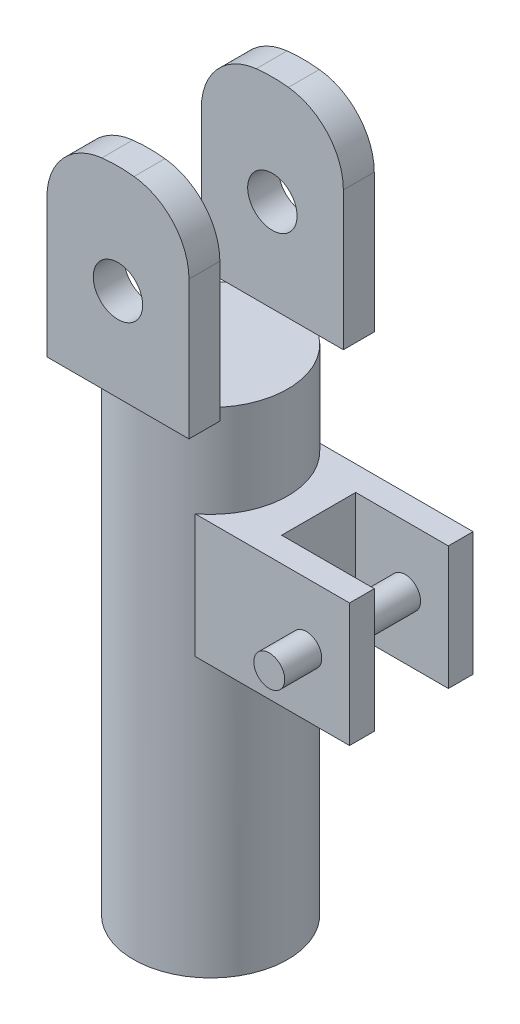
SolidWorks part; units mm, degrees
ref_plane "Front Plane" through (0, 0, 0) normal (0, 0, 1) x (1, 0, 0)
ref_plane "Top Plane" through (0, 0, 0) normal (0, 1, 0) x (1, 0, 0)
ref_plane "Right Plane" through (0, 0, 0) normal (1, 0, 0) x (0, 0, -1)
sketch "Sketch1" plane through (0, 0, 0) normal (0, 1, 0) x (1, 0, 0)
  circle A0 centre (0, 0) radius 12.5
  dimension "D1" = 25
extrude "Boss-Extrude1" add sketch "Sketch1" along normal blind 35
sketch "Sketch3" plane through (0, 0, 0) normal (0, 0, 1) x (1, 0, 0)
  line L5 (12.5, 35) -> (-12.5, 35) construction
  line L6 (12.5, 0) -> (12.5, 35) construction
  line L7 (0, 50) -> (0, 72.8405) construction
  line L8 (-11.5, 35) -> (11.5, 35)
  line L9 (11.5, 35) -> (11.5, 57.4167)
  line L10 (-11.5, 35) -> (-11.5, 57.4167)
  circle A2 centre (0, 50) radius 4
  arc A3 (-2.6077, 67.3551) -> (2.6077, 67.3551) centre (0, 43.9583) cw
  arc A4 (2.6077, 67.3551) -> (11.5, 57.4167) centre (1.5, 57.4167) cw
  arc A5 (-2.6077, 67.3551) -> (-11.5, 57.4167) centre (-1.5, 57.4167) ccw
  point P5 (11.5, 64.5)
  point P10 (-11.5, 64.5)
  dimension "D1" = 15
  dimension "D3" = 23
  dimension "D2" = 10
  dimension "D4" = 1
extrude "Boss-Extrude2" add sketch "Sketch3" along normal mid plane 30
sketch "Sketch4" plane through (0, 0, 0) normal (0, -1, 0) x (1, 0, 0)
  circle A0 centre (0, 0) radius 10
  dimension "D1" = 20
extrude "Cut-Extrude1" cut sketch "Sketch4" against normal blind 30
sketch "Sketch5" plane through (11.5, 0, 0) normal (1, 0, 0) x (0, 0, -1)
  line L0 (15, 67.5) -> (-15, 67.5) construction
  line L1 (-10, 67.5) -> (10, 67.5)
  line L2 (-10, 67.5) -> (-10, 35)
  line L3 (-10, 35) -> (10, 35)
  line L4 (10, 67.5) -> (10, 35)
  line L5 (-15, 35) -> (-4.899, 35) construction
  point P8 (0, 67.5)
  dimension "D1" = 20
extrude "Cut-Extrude2" cut sketch "Sketch5" against normal through all
sketch "Sketch6" plane through (0, 0, 0) normal (0, -1, 0) x (1, 0, 0)
  circle A0 centre (0, 0) radius 10 construction
  circle A1 centre (0, 0) radius 12.5
  circle A2 centre (0, 0) radius 12.5
  circle A3 centre (0, 0) radius 10
  dimension "D1" = 0
extrude "Boss-Extrude3" add sketch "Sketch6" along normal blind 45
sketch "Sketch9" plane through (0, 0, 0) normal (0, 0, 1) x (1, 0, 0)
  line L0 (12.5, -45) -> (12.5, 35) construction
  line L1 (13.5, 0) -> (32.5, 0)
  line L2 (13.5, 0) -> (13.5, 20)
  line L3 (13.5, 20) -> (32.5, 20)
  line L4 (32.5, 0) -> (32.5, 20)
  line L6 (-12.5, -45) -> (12.5, -45) construction
  dimension "D1" = 19
  dimension "D2" = 20
  dimension "D3" = 1
  dimension "D4" = 45
extrude "Boss-Extrude6" add sketch "Sketch9" along normal mid plane 20 separate body
sketch "Sketch10" plane through (13.5, 0, 0) normal (-1, 0, 0) x (0, 0, 1)
  line L4 (-10, 20) -> (-10, 0)
  line L5 (-10, 0) -> (10, 0)
  line L6 (10, 0) -> (10, 20)
  line L7 (10, 20) -> (-10, 20)
  line L8 (-10, 20) -> (-10, 0)
  line L9 (-10, 0) -> (10, 0)
  line L10 (10, 0) -> (10, 20)
  line L11 (10, 20) -> (-10, 20)
  dimension "D1" = 0
extrude "Boss-Extrude7" add sketch "Sketch10" along normal up to next
sketch "Sketch11" plane through (0, 20, 0) normal (0, 1, 0) x (1, 0, 0)
  line L0 (32.5, -10) -> (32.5, 10) construction
  line L1 (32.5, 6) -> (17.5, 6)
  line L2 (32.5, 6) -> (32.5, -6)
  line L3 (32.5, -6) -> (17.5, -6)
  line L4 (17.5, 6) -> (17.5, -6)
  line L5 (7.5, 10) -> (32.5, 10) construction
  dimension "D1" = 15
  dimension "D2" = 12
  dimension "D3" = 4
extrude "Cut-Extrude3" cut sketch "Sketch11" against normal blind 20
sketch "Sketch12" plane through (0, 0, -6) normal (0, 0, 1) x (1, 0, 0)
  line L0 (32.5, 0) -> (32.5, 20) construction
  line L1 (7.5, 20) -> (32.5, 20) construction
  circle A0 centre (25.5, 10) radius 2.5
  dimension "D1" = 5
  dimension "D2" = 7
  dimension "D3" = 10
extrude "Cut-Extrude4" cut sketch "Sketch12" against normal through all both and the other way through all
sketch "Sketch13" plane through (0, 0, 6) normal (0, 0, -1) x (-1, 0, 0)
  circle A0 centre (-25.5, 10) radius 2.5 construction
  circle A1 centre (-25.5, 10) radius 2.5
extrude "Boss-Extrude8" add sketch "Sketch13" along normal blind 20 and the other way blind 10
